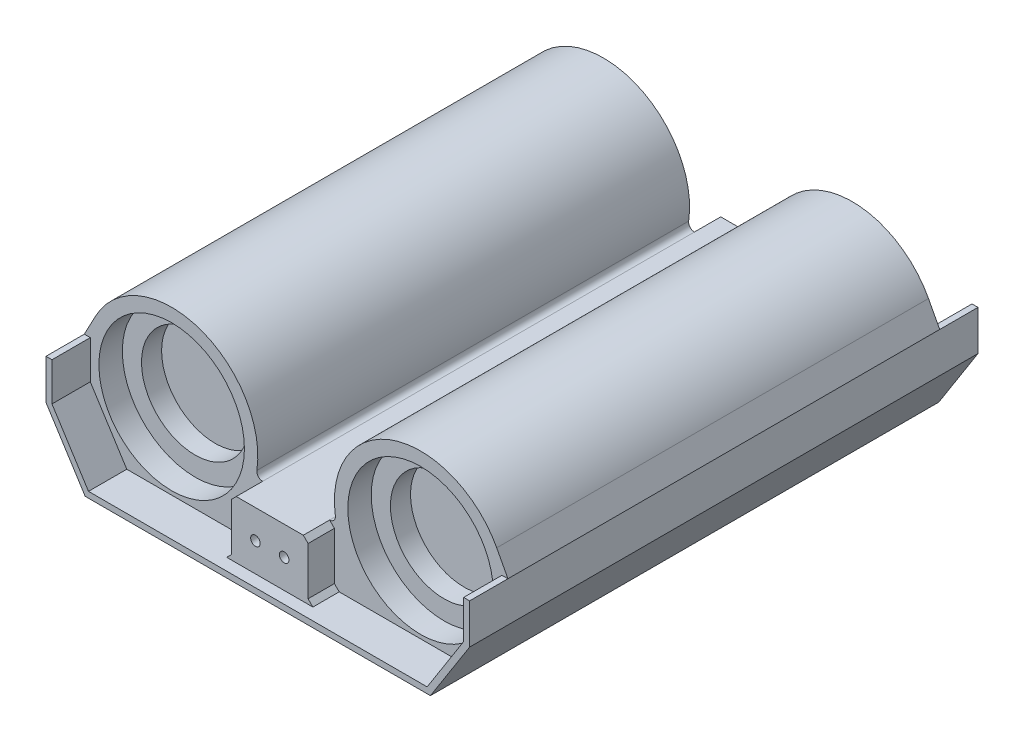
SolidWorks part; units mm, degrees
material "Thornel VCB-20 Carbon Cloth"
ref_plane "Front Plane" through (0, 0, 0) normal (0, 0, 1) x (1, 0, 0)
ref_plane "Top Plane" through (0, 0, 0) normal (0, 1, 0) x (1, 0, 0)
ref_plane "Right Plane" through (0, 0, 0) normal (1, 0, 0) x (0, 0, -1)
sketch "Sketch3" plane through (0, 0, 0) normal (0, 0, 1) x (1, 0, 0)
  line L0 (-7.5, -25) -> (7.5, -25) construction
  line L3 (-20, -10) -> (20, -10)
  line L4 (-20, -40) -> (-20, -10)
  line L5 (-20, -40) -> (20, -40)
  line L6 (20, -40) -> (20, -10)
  line L7 (0, -40) -> (0, -10) construction
  line L8 (0, -10) -> (0, 0) construction
  circle A2 centre (7.5, -25) radius 2.5
  circle A3 centre (-7.5, -25) radius 2.5
  point P11 (0, -25)
  dimension "D4" = 5
  dimension "D5" = 5
  dimension "D1" = 15
  dimension "D2" = 40
  dimension "D3" = 30
  dimension "D6" = 15
  dimension "D7" = 10
extrude "Boss-Extrude2" add sketch "Sketch3" along normal blind 6.25
sketch "Sketch4" plane through (0, 0, 6.25) normal (0, 0, 1) x (1, 0, 0)
  line L0 (20, -40) -> (20, -10) construction
  line L1 (-20, -40) -> (20, -40)
  line L2 (-20, -40) -> (-20, -33.75)
  line L3 (-20, -33.75) -> (20, -33.75)
  line L4 (20, -40) -> (20, -33.75)
  dimension "D1" = 6.25
extrude "Boss-Extrude3" add sketch "Sketch4" along normal blind 7.5
sketch "Sketch5" plane through (0, 0, 13.75) normal (0, 0, 1) x (1, 0, 0)
  line L1 (-20, -40) -> (-88.4287, -40)
  line L12 (-110.625, -10.9092) -> (-90.1451, -43.125)
  line L13 (0, -33.75) -> (0, -40) construction
  line L27 (-107.5, -10) -> (-88.4287, -40)
  line L29 (-107.5, 10) -> (-107.5, -10)
  line L30 (-107.5, 10) -> (-110.625, 10)
  line L31 (-110.625, 10) -> (-110.625, -10.9092)
  line L32 (110.625, 10) -> (110.625, -10.9092)
  line L33 (107.5, 10) -> (110.625, 10)
  line L34 (107.5, 10) -> (107.5, -10)
  line L35 (107.5, -10) -> (88.4287, -40)
  line L36 (110.625, -10.9092) -> (90.1451, -43.125)
  line L38 (20, -40) -> (88.4287, -40)
  line L39 (-90.1451, -43.125) -> (90.1451, -43.125)
  line L40 (-20, -40) -> (20, -40) construction
  line L41 (-20, -40) -> (20, -40)
  arc A1 (-104.9218, -10.3078) -> (-55, -40) centre (-65, 0) ccw construction
  arc A4 (104.9218, -10.3078) -> (55, -40) centre (65, 0) cw construction
  dimension "D3" = 3.125
  dimension "D2" = 3.125
  dimension "D4" = 3.125
  dimension "D7" = 20
  dimension "D1" = 10
  dimension "D5" = 42.5
  dimension "D6" = 50
  dimension "D8" = 65
extrude "Boss-Extrude4" add sketch "Sketch5" against normal blind 20
chamfer "Chamfer1" distance 2.5 angle 45 4 edges at (-20, -10, 3.125) (20, -10, 3.125) (-20, -40, 6.875) (20, -40, 6.875)
sketch "Sketch6" plane through (0, 0, 13.75) normal (0, 0, 1) x (1, 0, 0)
  line L0 (-110.625, 10) -> (-104.7676, 21.0604)
  line L1 (-90.1451, -43.125) -> (90.1451, -43.125) construction
  line L2 (-110.625, -10.9092) -> (-90.1451, -43.125) construction
  line L3 (-110.625, 10) -> (-110.625, -10.9092) construction
  line L4 (-90.1451, -43.125) -> (90.1451, -43.125)
  line L5 (-110.625, -10.9092) -> (-90.1451, -43.125)
  line L6 (-110.625, 10) -> (-110.625, -10.9092)
  line L7 (0, 0) -> (0, -43.125) construction
  line L9 (-65, 0) -> (0, 0) construction
  line L11 (17.5, -10) -> (-17.5, -10)
  line L15 (110.625, 10) -> (110.625, -10.9092)
  line L16 (110.625, -10.9092) -> (90.1451, -43.125)
  line L17 (110.625, 10) -> (104.7676, 21.0604)
  circle A1 centre (-65, 0) radius 38
  arc A3 (-20.4793, -6.5503) -> (-104.7676, 21.0604) centre (-65, 0) ccw
  arc A5 (-20.4793, -6.5503) -> (-17.5, -10) centre (-17.5, -6.9886) ccw
  arc A6 (20.4793, -6.5503) -> (17.5, -10) centre (17.5, -6.9886) cw
  arc A7 (20.4793, -6.5503) -> (104.7676, 21.0604) centre (65, 0) cw
  circle A8 centre (65, 0) radius 38
  point P26 (0, -10)
  dimension "D1" = 76
  dimension "D2" = 65
  dimension "D3" = 45
extrude "Boss-Extrude5" add sketch "Sketch6" along normal blind 12.25
sketch "Sketch8" plane through (0, 0, 26) normal (0, 0, 1) x (1, 0, 0)
  line L0 (-65, 0) -> (0, 0) construction
  line L1 (0, 0) -> (0, -43.125) construction
  line L2 (-90.1451, -43.125) -> (90.1451, -43.125) construction
  line L13 (-104.7676, 21.0604) -> (-110.625, 10)
  line L14 (-110.625, 10) -> (-110.625, -10.9092)
  line L15 (-110.625, -10.9092) -> (-90.1451, -43.125)
  line L16 (-90.1451, -43.125) -> (90.1451, -43.125)
  line L17 (90.1451, -43.125) -> (110.625, -10.9092)
  line L18 (110.625, -10.9092) -> (110.625, 10)
  line L19 (110.625, 10) -> (104.7676, 21.0604)
  line L21 (17.5, -10) -> (-17.5, -10)
  line L23 (-104.7676, 21.0604) -> (-110.625, 10)
  line L24 (-110.625, 10) -> (-110.625, -10.9092)
  line L25 (-110.625, -10.9092) -> (-90.1451, -43.125)
  line L26 (-90.1451, -43.125) -> (90.1451, -43.125)
  line L27 (90.1451, -43.125) -> (110.625, -10.9092)
  line L28 (110.625, -10.9092) -> (110.625, 10)
  line L29 (110.625, 10) -> (104.7676, 21.0604)
  line L31 (17.5, -10) -> (-17.5, -10)
  circle A0 centre (-65, 0) radius 28
  circle A1 centre (65, 0) radius 28
  arc A5 (-20.4793, -6.5503) -> (-104.7676, 21.0604) centre (-65, 0) ccw
  arc A6 (104.7676, 21.0604) -> (20.4793, -6.5503) centre (65, 0) ccw
  arc A7 (17.5, -10) -> (20.4793, -6.5503) centre (17.5, -6.9886) ccw
  arc A8 (-20.4793, -6.5503) -> (-17.5, -10) centre (-17.5, -6.9886) ccw
  arc A9 (-20.4793, -6.5503) -> (-104.7676, 21.0604) centre (-65, 0) ccw
  arc A10 (104.7676, 21.0604) -> (20.4793, -6.5503) centre (65, 0) ccw
  arc A11 (17.5, -10) -> (20.4793, -6.5503) centre (17.5, -6.9886) ccw
  arc A12 (-20.4793, -6.5503) -> (-17.5, -10) centre (-17.5, -6.9886) ccw
  dimension "D1" = 56
  dimension "D2" = 0
extrude "Boss-Extrude7" add sketch "Sketch8" along normal blind 10.5
sketch "Sketch9" plane through (0, 0, 36.5) normal (0, 0, 1) x (1, 0, 0)
  line L0 (0, 0) -> (0, -43.125) construction
  line L1 (-90.1451, -43.125) -> (90.1451, -43.125) construction
  circle A2 centre (65, 0) radius 31.125
  circle A3 centre (-65, 0) radius 31.125
  circle A4 centre (-65, 0) radius 31.125
  dimension "D1" = 3.125
extrude "Boss-Extrude8" add sketch "Sketch9" along normal blind 3.125
fillet "Fillet1" radius 4 2 edges at (33.875, 0, 36.5) (-33.875, 0, 36.5)
sketch "Sketch10" plane through (0, 0, 36.5) normal (0, 0, 1) x (1, 0, 0)
  line L10 (-104.7676, 21.0604) -> (-110.625, 10)
  line L11 (-110.625, 10) -> (-110.625, -10.9092)
  line L12 (-110.625, -10.9092) -> (-90.1451, -43.125)
  line L13 (-90.1451, -43.125) -> (90.1451, -43.125)
  line L14 (90.1451, -43.125) -> (110.625, -10.9092)
  line L15 (110.625, -10.9092) -> (110.625, 10)
  line L16 (110.625, 10) -> (104.7676, 21.0604)
  line L18 (17.5, -10) -> (-17.5, -10)
  line L20 (-104.7676, 21.0604) -> (-110.625, 10)
  line L21 (-110.625, 10) -> (-110.625, -10.9092)
  line L22 (-110.625, -10.9092) -> (-90.1451, -43.125)
  line L23 (-90.1451, -43.125) -> (-47.5, -43.125)
  line L24 (90.1451, -43.125) -> (110.625, -10.9092)
  line L25 (110.625, -10.9092) -> (110.625, 10)
  line L26 (110.625, 10) -> (104.7676, 21.0604)
  line L28 (17.5, -10) -> (-17.5, -10)
  line L30 (-47.5, -43.125) -> (-47.5, -40)
  line L31 (47.5, -43.125) -> (47.5, -40)
  line L32 (47.5, -43.125) -> (90.1451, -43.125)
  line L33 (47.5, -40) -> (88.4287, -40)
  line L40 (-102.006, 19.5978) -> (-107.5, 9.2236)
  line L41 (-107.5, 9.2236) -> (-107.5, -10)
  line L42 (-107.5, -10) -> (-88.4287, -40)
  line L43 (-88.4287, -40) -> (88.4287, -40)
  line L44 (88.4287, -40) -> (107.5, -10)
  line L45 (107.5, -10) -> (107.5, 9.2236)
  line L46 (107.5, 9.2236) -> (102.006, 19.5978)
  line L48 (17.5, -13.125) -> (-17.5, -13.125)
  line L50 (-102.006, 19.5978) -> (-107.5, 9.2236)
  line L51 (-107.5, 9.2236) -> (-107.5, -10)
  line L52 (-107.5, -10) -> (-88.4287, -40)
  line L53 (-88.4287, -40) -> (-47.5, -40)
  line L54 (88.4287, -40) -> (107.5, -10)
  line L55 (107.5, -10) -> (107.5, 9.2236)
  line L56 (107.5, 9.2236) -> (102.006, 19.5978)
  line L58 (17.5, -13.125) -> (-17.5, -13.125)
  arc A4 (-20.4793, -6.5503) -> (-104.7676, 21.0604) centre (-65, 0) ccw
  arc A5 (104.7676, 21.0604) -> (20.4793, -6.5503) centre (65, 0) ccw
  arc A6 (17.5, -10) -> (20.4793, -6.5503) centre (17.5, -6.9886) ccw
  arc A7 (-20.4793, -6.5503) -> (-17.5, -10) centre (-17.5, -6.9886) ccw
  arc A8 (-20.4793, -6.5503) -> (-104.7676, 21.0604) centre (-65, 0) ccw
  arc A9 (104.7676, 21.0604) -> (20.4793, -6.5503) centre (65, 0) ccw
  arc A10 (17.5, -10) -> (20.4793, -6.5503) centre (17.5, -6.9886) ccw
  arc A11 (-20.4793, -6.5503) -> (-17.5, -10) centre (-17.5, -6.9886) ccw
  arc A16 (-23.571, -6.0954) -> (-102.006, 19.5978) centre (-65, 0) ccw
  arc A17 (102.006, 19.5978) -> (23.571, -6.0954) centre (65, 0) ccw
  arc A18 (17.5, -13.125) -> (23.571, -6.0954) centre (17.5, -6.9886) ccw
  arc A19 (-23.571, -6.0954) -> (-17.5, -13.125) centre (-17.5, -6.9886) ccw
  arc A20 (-23.571, -6.0954) -> (-102.006, 19.5978) centre (-65, 0) ccw
  arc A21 (102.006, 19.5978) -> (23.571, -6.0954) centre (65, 0) ccw
  arc A22 (17.5, -13.125) -> (23.571, -6.0954) centre (17.5, -6.9886) ccw
  arc A23 (-23.571, -6.0954) -> (-17.5, -13.125) centre (-17.5, -6.9886) ccw
  dimension "D3" = 47.5
  dimension "D4" = 47.5
  dimension "D1" = 0
  dimension "D2" = 3.125
extrude "Boss-Extrude9" add sketch "Sketch10" along normal blind 90
mirror "Mirror1" about plane through (-65, 0, 126.5) normal (0, 0, 1) of "Boss-Extrude2", "Boss-Extrude3", "Boss-Extrude4", "Chamfer1", "Boss-Extrude5", "Boss-Extrude7", "Boss-Extrude8", "Fillet1", "Boss-Extrude9"
ref_plane "Plane1" through (0, 0, 126.5) normal (0, 0, -1) x (-1, 0, 0)
sketch "Sketch12" plane through (0, 0, 253) normal (0, 0, 1) x (1, 0, 0)
  line L8 (-20, -12.5) -> (-20, -37.5)
  line L9 (-20, -37.5) -> (-22.5, -40)
  line L10 (-22.5, -40) -> (22.5, -40)
  line L11 (22.5, -40) -> (20, -37.5)
  line L12 (20, -37.5) -> (20, -12.5)
  line L13 (20, -12.5) -> (17.5, -10)
  line L14 (17.5, -10) -> (-17.5, -10)
  line L15 (-17.5, -10) -> (-20, -12.5)
  line L16 (-20, -12.5) -> (-20, -37.5)
  line L17 (-20, -37.5) -> (-22.5, -40)
  line L18 (-22.5, -40) -> (22.5, -40)
  line L19 (22.5, -40) -> (20, -37.5)
  line L20 (20, -37.5) -> (20, -12.5)
  line L21 (20, -12.5) -> (17.5, -10)
  line L22 (17.5, -10) -> (-17.5, -10)
  line L23 (-17.5, -10) -> (-20, -12.5)
  circle A0 centre (7.5, -25) radius 2.5 construction
  circle A1 centre (-7.5, -25) radius 2.5 construction
  circle A2 centre (7.5, -25) radius 2.5
  circle A3 centre (-7.5, -25) radius 2.5
  dimension "D1" = 0
extrude "Boss-Extrude10" add sketch "Sketch12" against normal blind 30
mirror "Mirror2" about plane through (0, 0, 126.5) normal (0, 0, -1) of "Boss-Extrude10"
sketch "Sketch13" plane through (0, 0, 0) normal (1, 0, 0) x (0, 0, -1)
  line L0 (-216.5, -43.125) -> (-41.5, -43.125)
  line L1 (-36.5, -38.125) -> (-36.5, -25.2895)
  line L2 (-36.5, 35.0281) -> (-36.5, -35.0281) construction
  line L3 (-41.5, -20.2895) -> (-126.5, -20.2895)
  arc A0 (-36.5, -25.2895) -> (-41.5, -20.2895) centre (-41.5, -25.2895) ccw
  arc A1 (-41.5, -43.125) -> (-36.5, -38.125) centre (-41.5, -38.125) ccw
  point P10 (-36.5, -20.2895)
  point P13 (-36.5, -43.125)
  dimension "D1" = 5
sketch "Sketch14" plane through (0, -43.125, 0) normal (0, -1, 0) x (1, 0, 0)
  line L0 (0, 259.25) -> (0, 237.75) construction
  line L1 (-90.1451, 259.25) -> (90.1451, 259.25) construction
  line L2 (-10, 237.75) -> (10, 237.75) construction
  line L3 (-47.5, 126.5) -> (47.5, 126.5) construction
  line L4 (-47.5, 216.5) -> (-47.5, 36.5) construction
  line L5 (47.5, 216.5) -> (47.5, 36.5) construction
  line L6 (-10, 15.25) -> (10, 15.25) construction
  line L7 (0, -6.25) -> (0, 15.25) construction
  circle A0 centre (10, 237.75) radius 2.5
  circle A1 centre (-10, 237.75) radius 2.5
  circle A2 centre (-10, 15.25) radius 2.5
  circle A3 centre (10, 15.25) radius 2.5
  dimension "D3" = 5
  dimension "D1" = 21.5
  dimension "D2" = 10
extrude "Cut-Extrude1" cut sketch "Sketch14" against normal blind 10
equation "\"a\"=3.125"
equation "\"D3@Sketch5\"=\"a\""
equation "\"D2@Sketch5\"=\"a\""
equation "\"D4@Sketch5\"=\"a\""
